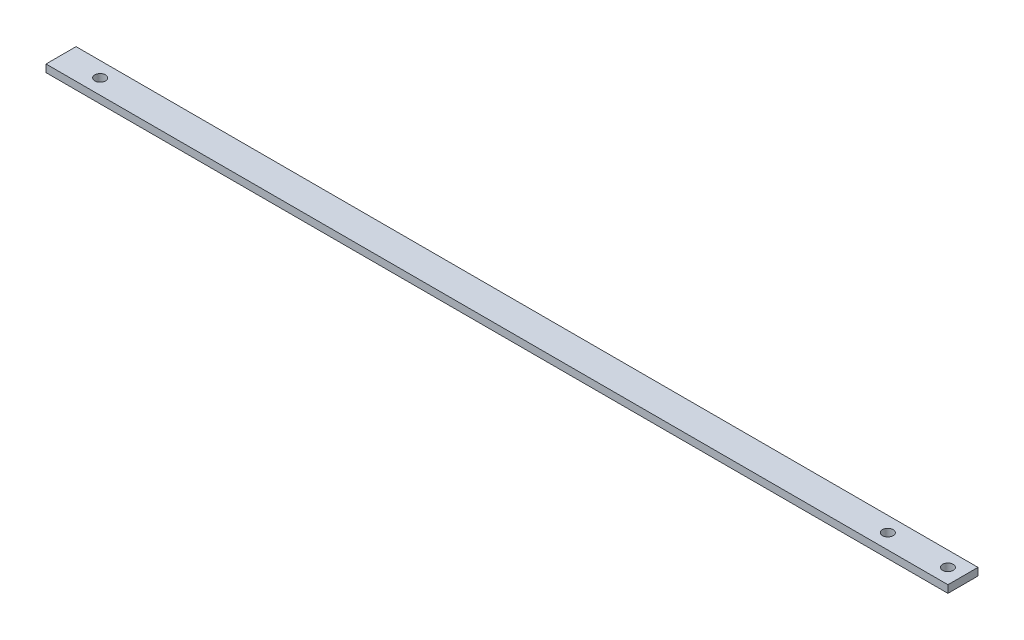
SolidWorks part; units mm, degrees
ref_plane "Front Plane" through (0, 0, 0) normal (0, 0, 1) x (1, 0, 0)
ref_plane "Top Plane" through (0, 0, 0) normal (0, 1, 0) x (1, 0, 0)
ref_plane "Right Plane" through (0, 0, 0) normal (1, 0, 0) x (0, 0, -1)
sketch "Sketch1" plane through (0, 0, 0) normal (0, 1, 0) x (1, 0, 0)
  line L0 (0, 6.35) -> (16.5354, 6.35)
  line L1 (0, 0) -> (381, 0)
  line L2 (0, 0) -> (0, 12.7)
  line L3 (0, 12.7) -> (381, 12.7)
  line L4 (381, 0) -> (381, 12.7)
  circle A0 centre (16.5354, 6.35) radius 2.2479
  circle A1 centre (349.25, 6.35) radius 2.2479
  circle A2 centre (374.65, 6.35) radius 2.2479
  dimension "D1" = 381
  dimension "D2" = 12.7
  dimension "D3" = 16.5354
extrude "Boss-Extrude2" add sketch "Sketch1" along normal blind 3.175 contours A0 L2 L1 L4 L3 A2 A1 region at (189.9403, 0, -6.35)
